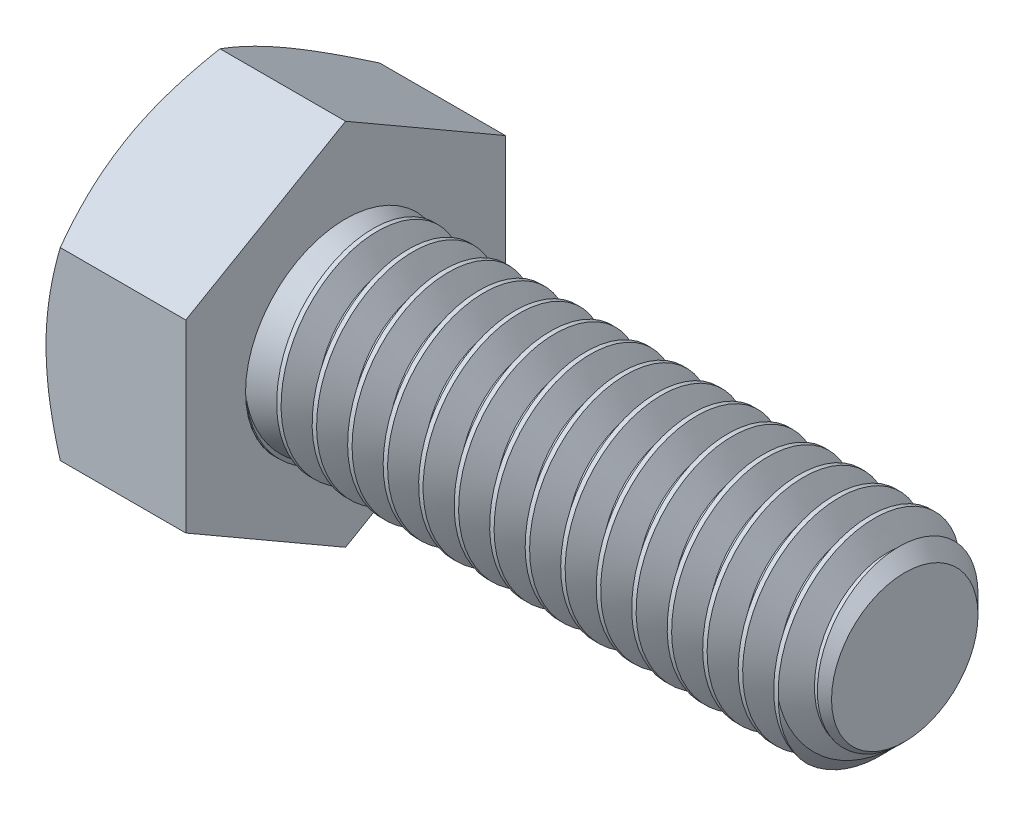
SolidWorks part; units mm, degrees
note: '?' marks a value the reader was unsure of.
ref_plane "Front Plane" through (0, 0, 0) normal (0, 0, 1) x (1, 0, 0)
ref_plane "Top Plane" through (0, 0, 0) normal (0, 1, 0) x (1, 0, 0)
ref_plane "Right Plane" through (0, 0, 0) normal (1, 0, 0) x (0, 0, -1)
sketch "Sketch1" plane through (0, 0, 0) normal (0, 0, 1) x (1, 0, 0)
  line L0 (-13.8906, 0) -> (13.8906, 0) construction
  line L1 (13.8906, 3.9688) -> (13.8906, -3.9688) construction
  line L2 (-8.3344, 6.35) -> (-8.3344, -6.35) construction
  line L3 (-13.8906, 6.35) -> (-13.8906, -6.35) construction
  line L4 (-8.5884, 3.975) -> (-8.3344, 3.975) construction
  line L5 (-8.3344, 3.975) -> (-1.4495, 0) construction
  line L6 (-8.5884, 3.975) -> (-8.5884, 0) construction
  line L7 (-8.3344, 0) -> (-8.3344, 3.975) construction
  point P9 (-8.3344, 0)
  point P10 (8.9517, -3.9688)
  dimension "Screw Dia" = 7.9375
  dimension "Hex" = 12.7
  dimension "Head Ht" = 5.5562
  dimension "Screw Length" = 22.225
  dimension "D1" = 4.9389
  dimension "D2" = 30
  dimension "D3" = 0.254
  dimension "MinThread" = 22.225
  dimension "D4" = 0.0124
ref_plane "Plane2" through (13.8906, 0, 0) normal (1, 0, 0) x (0, 0, -1)
sketch "Sketch5" plane through (13.8906, 0, 0) normal (1, 0, 0) x (0, 0, -1)
  circle A0 centre (0, 0) radius 3.9688
extrude "Boss-Extrude3" add sketch "Sketch5" against normal up to vertex (22.225 mm away) up to point (-8.3344, 0, 0)
sketch "Sketch9" plane through (13.8906, 0, 0) normal (1, 0, 0) x (0, 0, -1)
  circle A1 centre (0, 0) radius 3.9688
  circle A2 centre (0, 0) radius 3.9688
  dimension "D1" = 0
chamfer "Chamfer1" distance 1.0583 angle 45 1 edges at (13.8906, 0, -3.9688)
sketch "Sketch6" plane through (-8.3344, 0, 0) normal (-1, 0, 0) x (0, 0, 1)
  line L0 (0, 6.35) -> (0, -6.35) construction
  line L1 (6.35, 3.6662) -> (0, 7.3323)
  line L2 (0, 7.3323) -> (-6.35, 3.6662)
  line L3 (-6.35, 3.6662) -> (-6.35, -3.6662)
  line L4 (-6.35, -3.6662) -> (0, -7.3323)
  line L5 (0, -7.3323) -> (6.35, -3.6662)
  line L6 (6.35, -3.6662) -> (6.35, 3.6662)
  circle A0 centre (0, 0) radius 6.35 construction
extrude "Boss-Extrude4" add sketch "Sketch6" along normal up to vertex (5.5563 mm away) separate body up to point (-13.8906, -6.35, 0)
sketch "Sketch7" plane through (-13.8906, 0, 0) normal (-1, 0, 0) x (0, 0, 1)
  circle A0 centre (0, 0) radius 6.35 construction
  circle A1 centre (0, 0) radius 6.35
sketch "Sketch8" plane through (-13.8906, 0, 0) normal (-1, 0, 0) x (0, 0, 1)
  circle A0 centre (0, 0) radius 6.35 construction
  circle A1 centre (0, 0) radius 6.35
extrude "Cut-Extrude3" cut sketch "Sketch8" against normal through all draft 60 flip side to cut
sketch "Sketch12" plane through (-13.8906, 0, 0) normal (-1, 0, 0) x (0, 0, 1)
  line L0 (0, 4.8895) -> (0, 2.7305) construction
  line L1 (0.1905, 4.8895) -> (0.1905, 2.7305)
  line L2 (-0.1905, 4.8895) -> (-0.1905, 2.7305)
  line L3 (0, 3.9688) -> (0, -3.9688) construction
  arc A0 (0.1905, 4.8895) -> (-0.1905, 4.8895) centre (0, 4.8895) ccw
  arc A1 (-0.1905, 2.7305) -> (0.1905, 2.7305) centre (0, 2.7305) ccw
  circle A3 centre (0, 0) radius 2.54 construction
  circle A4 centre (0, 0) radius 5.08 construction
  point P2 (0, 3.81)
  dimension "D1" = 5.08
  dimension "D3" = 10.16
  dimension "D2" = 0.381
extrude "Cut-Extrude4" cut sketch "Sketch12" against normal blind 0.254
pattern_circular "CirPattern1" count 6 over 360 about axis through (0, 0, 0) along (1, 0, 0) of "Cut-Extrude4"
curve "Helix/Spiral1" pitch 1.4111 height 23.6361 turns 16.75 parameters "Pitch"=1.4111
sketch "Sketch10" plane through (0, 0, 0) normal (0, 0, 1) x (1, 0, 0)
  line L0 (13.8906, 3.9688) -> (14.4198, 3.0522)
  line L1 (14.4198, 3.0522) -> (14.5962, 3.0522)
  line L2 (14.5962, 3.0522) -> (15.1253, 3.9687)
  line L3 (13.8906, 3.9688) -> (15.1253, 3.9687)
  line L4 (14.508, 3.9688) -> (14.508, 3.0522) construction
  line L5 (14.1552, 3.5105) -> (14.8608, 3.5105) construction
  dimension "D1" = 60
  dimension "D2" = 0.1764
  dimension "D3" = 0.7056
sweep "Cut-Sweep1" cut profiles "Sketch10" path "Helix/Spiral1" align with end faces yes
sketch "Sketch13" plane through (0, 0, 0) normal (0, 0, 1) x (1, 0, 0)
  line L0 (-13.8906, 0) -> (13.8906, 0) construction
  line L1 (-8.3344, 3.975) -> (-1.4495, 0) construction
  line L2 (-8.5884, 3.975) -> (-8.3344, 3.975) construction
  line L3 (-8.5884, 3.975) -> (-8.5884, 0) construction
  line L4 (-8.5884, 0) -> (-1.4495, 0)
  line L5 (-8.3344, 3.975) -> (-1.4495, 0)
  line L6 (-8.5884, 3.975) -> (-8.3344, 3.975)
  line L7 (-8.5884, 3.975) -> (-8.5884, 0)
revolve "Revolve7" add sketch "Sketch13" angle 360 about L4
ref_axis "Center Axis 1" through (-8.3236, 0, 0) along (1, 0, 0)?
ref_plane "Contact Plane 1" through (-8.3344, 0, 0) normal (1, 0, 0) x (0, 0, -1)
equation "\"D2@Sketch10\" = \"Pitch@Helix/Spiral1\"*.125"
equation "\"D3@Sketch10\" = \"Pitch@Helix/Spiral1\"*.5"
equation "\"D3@Helix/Spiral1\" = \"Screw Length@Sketch1\" + \"Pitch@Helix/Spiral1\""
equation "\"D1@Chamfer1\" = \"Pitch@Helix/Spiral1\"*.75"
equation "\"D1@Sketch12\" = \"Hex@Sketch1\"*.4"
equation "\"D3@Sketch12\" = \"Hex@Sketch1\"*.8"
equation "\"D2@Sketch12\" = \"Hex@Sketch1\"*.03"
equation "\"D1@Sketch1\" = \"Pitch@Helix/Spiral1\"*3.5"
